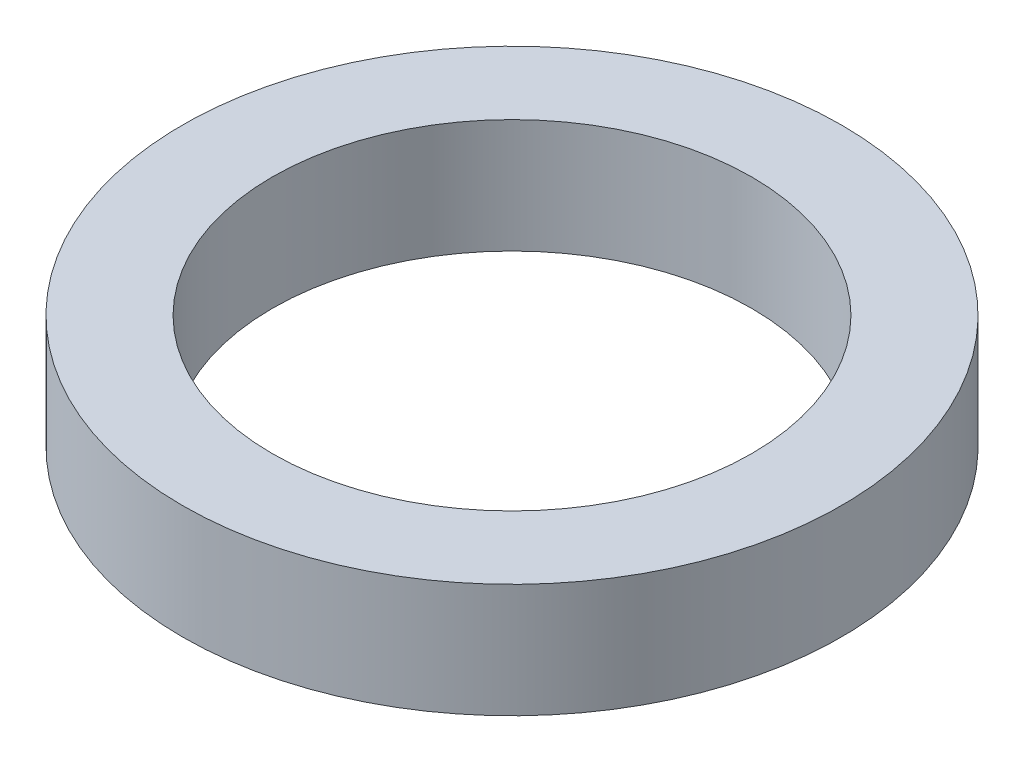
SolidWorks part; units mm, degrees
ref_plane "Front Plane" through (0, 0, 0) normal (0, 0, 1) x (1, 0, 0)
ref_plane "Top Plane" through (0, 0, 0) normal (0, 1, 0) x (1, 0, 0)
ref_plane "Right Plane" through (0, 0, 0) normal (1, 0, 0) x (0, 0, -1)
sketch "Sketch1" plane through (0, 0, 0) normal (0, 1, 0) x (1, 0, 0)
  circle A0 centre (0, 0) radius 55
  dimension "FLANGE_OD" = 110
extrude "Boss-Extrude1" add sketch "Sketch1" along normal blind 19
sketch "Sketch2" plane through (0, 0, 0) normal (0, 1, 0) x (1, 0, 0)
  circle A0 centre (0, 0) radius 40
  dimension "BORE_D" = 80
extrude "Cut-Extrude1" cut sketch "Sketch2" along normal through all
sketch "Sketch3" plane through (0, 19, 0) normal (0, 1, 0) x (1, 0, 0)
  circle A0 centre (0, 0) radius 23.5596 construction
  circle A1 centre (-23.5596, 0) radius 1.5977
  dimension "BOLT_D" = 3.1955
  dimension "BOLT_PCD" = 47.1191
extrude "Cut-Extrude2" cut sketch "Sketch3" against normal blind 11.6039 rebuild error yes
pattern_circular "CirPattern1" count 6 over 360 rebuild error yes
